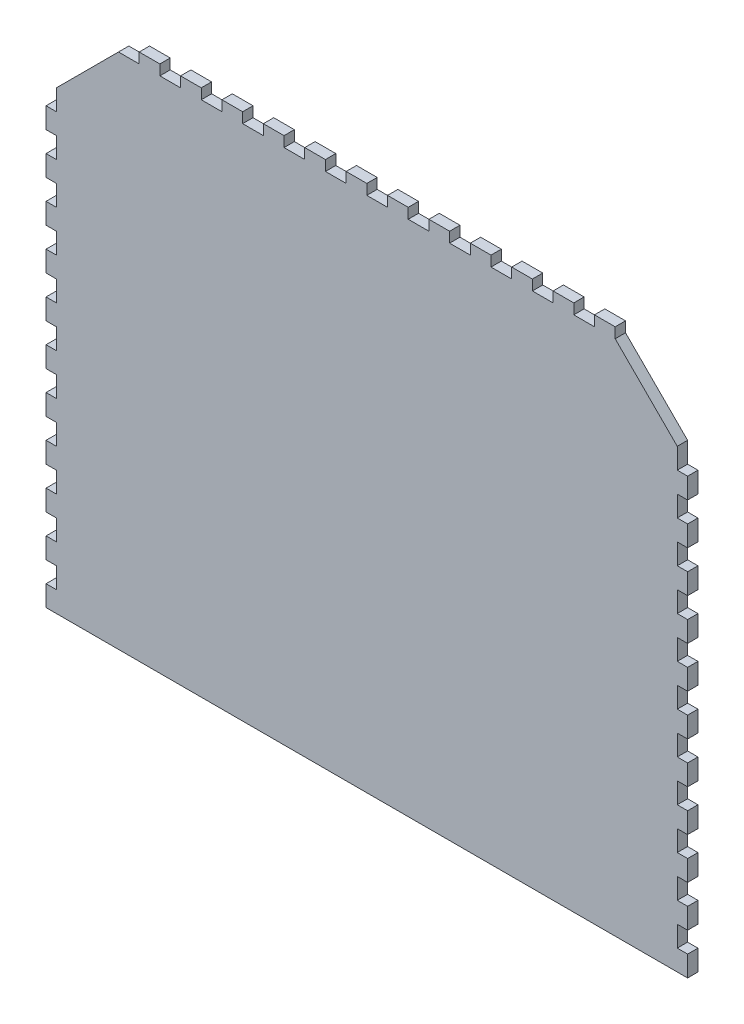
SolidWorks part; units mm, degrees
material "Buche"
ref_plane "Ebene vorne" through (0, 0, 0) normal (0, 0, 1) x (1, 0, 0)
ref_plane "Ebene oben" through (0, 0, 0) normal (0, 1, 0) x (1, 0, 0)
ref_plane "Ebene rechts" through (0, 0, 0) normal (1, 0, 0) x (0, 0, -1)
sketch "Skizze1" plane through (0, 0, 0) normal (0, 0, 1) x (1, 0, 0)
  line L0 (430.8962, 326.3402) -> (430.8962, 336.3402)
  line L1 (430.8962, 316.3402) -> (730.8962, 316.3402)
  line L2 (730.8962, 326.3402) -> (730.8962, 336.3402)
  line L3 (480.8962, 566.3402) -> (490.8962, 566.3402)
  line L4 (430.8962, 536.3402) -> (460.8962, 566.3402)
  line L5 (730.8962, 536.3402) -> (700.8962, 566.3402)
  line L6 (460.8962, 566.3402) -> (470.8962, 566.3402)
  line L7 (470.8962, 566.3402) -> (470.8962, 571.3402)
  line L8 (470.8962, 571.3402) -> (480.8962, 571.3402)
  line L9 (480.8962, 571.3402) -> (480.8962, 566.3402)
  line L10 (490.8962, 566.3402) -> (490.8962, 571.3402)
  line L11 (490.8962, 571.3402) -> (500.8962, 571.3402)
  line L12 (500.8962, 571.3402) -> (500.8962, 566.3402)
  line L13 (730.8962, 316.3402) -> (735.8962, 316.3402)
  line L14 (735.8962, 316.3402) -> (735.8962, 326.3402)
  line L15 (735.8962, 326.3402) -> (730.8962, 326.3402)
  line L16 (730.8962, 346.3402) -> (730.8962, 356.3402)
  line L17 (730.8962, 336.3402) -> (735.8962, 336.3402)
  line L18 (735.8962, 336.3402) -> (735.8962, 346.3402)
  line L19 (735.8962, 346.3402) -> (730.8962, 346.3402)
  line L20 (730.8962, 366.3402) -> (730.8962, 376.3402)
  line L21 (730.8962, 356.3402) -> (735.8962, 356.3402)
  line L22 (735.8962, 356.3402) -> (735.8962, 366.3402)
  line L23 (735.8962, 366.3402) -> (730.8962, 366.3402)
  line L24 (730.8962, 386.3402) -> (730.8962, 396.3402)
  line L25 (730.8962, 376.3402) -> (735.8962, 376.3402)
  line L26 (735.8962, 376.3402) -> (735.8962, 386.3402)
  line L27 (735.8962, 386.3402) -> (730.8962, 386.3402)
  line L28 (730.8962, 406.3402) -> (730.8962, 416.3402)
  line L29 (730.8962, 396.3402) -> (735.8962, 396.3402)
  line L30 (735.8962, 396.3402) -> (735.8962, 406.3402)
  line L31 (735.8962, 406.3402) -> (730.8962, 406.3402)
  line L32 (730.8962, 426.3402) -> (730.8962, 436.3402)
  line L33 (730.8962, 416.3402) -> (735.8962, 416.3402)
  line L34 (735.8962, 416.3402) -> (735.8962, 426.3402)
  line L35 (735.8962, 426.3402) -> (730.8962, 426.3402)
  line L36 (730.8962, 446.3402) -> (730.8962, 456.3402)
  line L37 (730.8962, 436.3402) -> (735.8962, 436.3402)
  line L38 (735.8962, 436.3402) -> (735.8962, 446.3402)
  line L39 (735.8962, 446.3402) -> (730.8962, 446.3402)
  line L40 (730.8962, 466.3402) -> (730.8962, 476.3402)
  line L41 (730.8962, 456.3402) -> (735.8962, 456.3402)
  line L42 (735.8962, 456.3402) -> (735.8962, 466.3402)
  line L43 (735.8962, 466.3402) -> (730.8962, 466.3402)
  line L44 (730.8962, 486.3402) -> (730.8962, 496.3402)
  line L45 (730.8962, 476.3402) -> (735.8962, 476.3402)
  line L46 (735.8962, 476.3402) -> (735.8962, 486.3402)
  line L47 (735.8962, 486.3402) -> (730.8962, 486.3402)
  line L48 (730.8962, 506.3402) -> (730.8962, 516.3402)
  line L49 (730.8962, 496.3402) -> (735.8962, 496.3402)
  line L50 (735.8962, 496.3402) -> (735.8962, 506.3402)
  line L51 (735.8962, 506.3402) -> (730.8962, 506.3402)
  line L52 (730.8962, 526.3402) -> (730.8962, 536.3402)
  line L53 (730.8962, 516.3402) -> (735.8962, 516.3402)
  line L54 (735.8962, 516.3402) -> (735.8962, 526.3402)
  line L55 (735.8962, 526.3402) -> (730.8962, 526.3402)
  line L56 (430.8962, 316.3402) -> (425.8962, 316.3402)
  line L57 (425.8962, 316.3402) -> (425.8962, 326.3402)
  line L58 (425.8962, 326.3402) -> (430.8962, 326.3402)
  line L59 (430.8962, 346.3402) -> (430.8962, 356.3402)
  line L60 (425.8962, 336.3402) -> (425.8962, 346.3402)
  line L61 (425.8962, 346.3402) -> (430.8962, 346.3402)
  line L62 (430.8962, 366.3402) -> (430.8962, 376.3402)
  line L63 (425.8962, 356.3402) -> (425.8962, 366.3402)
  line L64 (425.8962, 366.3402) -> (430.8962, 366.3402)
  line L65 (430.8962, 386.3402) -> (430.8962, 396.3402)
  line L66 (425.8962, 376.3402) -> (425.8962, 386.3402)
  line L67 (425.8962, 386.3402) -> (430.8962, 386.3402)
  line L68 (430.8962, 406.3402) -> (430.8962, 416.3402)
  line L69 (425.8962, 396.3402) -> (425.8962, 406.3402)
  line L70 (425.8962, 406.3402) -> (430.8962, 406.3402)
  line L71 (430.8962, 426.3402) -> (430.8962, 436.3402)
  line L72 (425.8962, 416.3402) -> (425.8962, 426.3402)
  line L73 (425.8962, 426.3402) -> (430.8962, 426.3402)
  line L74 (430.8962, 446.3402) -> (430.8962, 456.3402)
  line L75 (425.8962, 436.3402) -> (425.8962, 446.3402)
  line L76 (425.8962, 446.3402) -> (430.8962, 446.3402)
  line L77 (430.8962, 466.3402) -> (430.8962, 476.3402)
  line L78 (425.8962, 456.3402) -> (425.8962, 466.3402)
  line L79 (425.8962, 466.3402) -> (430.8962, 466.3402)
  line L80 (430.8962, 486.3402) -> (430.8962, 496.3402)
  line L81 (425.8962, 476.3402) -> (425.8962, 486.3402)
  line L82 (425.8962, 486.3402) -> (430.8962, 486.3402)
  line L83 (430.8962, 506.3402) -> (430.8962, 516.3402)
  line L84 (425.8962, 496.3402) -> (425.8962, 506.3402)
  line L85 (425.8962, 506.3402) -> (430.8962, 506.3402)
  line L86 (430.8962, 526.3402) -> (430.8962, 536.3402)
  line L87 (425.8962, 516.3402) -> (425.8962, 526.3402)
  line L88 (425.8962, 526.3402) -> (430.8962, 526.3402)
  line L89 (425.8962, 336.3402) -> (430.8962, 336.3402)
  line L90 (425.8962, 356.3402) -> (430.8962, 356.3402)
  line L91 (425.8962, 376.3402) -> (430.8962, 376.3402)
  line L92 (425.8962, 396.3402) -> (430.8962, 396.3402)
  line L93 (425.8962, 416.3402) -> (430.8962, 416.3402)
  line L94 (425.8962, 436.3402) -> (430.8962, 436.3402)
  line L95 (425.8962, 456.3402) -> (430.8962, 456.3402)
  line L96 (425.8962, 476.3402) -> (430.8962, 476.3402)
  line L97 (425.8962, 496.3402) -> (430.8962, 496.3402)
  line L98 (425.8962, 516.3402) -> (430.8962, 516.3402)
  line L99 (500.8962, 566.3402) -> (510.8962, 566.3402)
  line L100 (510.8962, 566.3402) -> (510.8962, 571.3402)
  line L101 (510.8962, 571.3402) -> (520.8962, 571.3402)
  line L102 (520.8962, 571.3402) -> (520.8962, 566.3402)
  line L103 (520.8962, 566.3402) -> (530.8962, 566.3402)
  line L104 (530.8962, 566.3402) -> (530.8962, 571.3402)
  line L105 (530.8962, 571.3402) -> (540.8962, 571.3402)
  line L106 (540.8962, 571.3402) -> (540.8962, 566.3402)
  line L107 (540.8962, 566.3402) -> (550.8962, 566.3402)
  line L108 (550.8962, 566.3402) -> (550.8962, 571.3402)
  line L109 (550.8962, 571.3402) -> (560.8962, 571.3402)
  line L110 (560.8962, 571.3402) -> (560.8962, 566.3402)
  line L111 (560.8962, 566.3402) -> (570.8962, 566.3402)
  line L112 (570.8962, 566.3402) -> (570.8962, 571.3402)
  line L113 (570.8962, 571.3402) -> (580.8962, 571.3402)
  line L114 (580.8962, 571.3402) -> (580.8962, 566.3402)
  line L115 (580.8962, 566.3402) -> (590.8962, 566.3402)
  line L116 (590.8962, 566.3402) -> (590.8962, 571.3402)
  line L117 (590.8962, 571.3402) -> (600.8962, 571.3402)
  line L118 (600.8962, 571.3402) -> (600.8962, 566.3402)
  line L119 (600.8962, 566.3402) -> (610.8962, 566.3402)
  line L120 (610.8962, 566.3402) -> (610.8962, 571.3402)
  line L121 (610.8962, 571.3402) -> (620.8962, 571.3402)
  line L122 (620.8962, 571.3402) -> (620.8962, 566.3402)
  line L123 (620.8962, 566.3402) -> (630.8962, 566.3402)
  line L124 (630.8962, 566.3402) -> (630.8962, 571.3402)
  line L125 (630.8962, 571.3402) -> (640.8962, 571.3402)
  line L126 (640.8962, 571.3402) -> (640.8962, 566.3402)
  line L127 (640.8962, 566.3402) -> (650.8962, 566.3402)
  line L128 (650.8962, 566.3402) -> (650.8962, 571.3402)
  line L129 (650.8962, 571.3402) -> (660.8962, 571.3402)
  line L130 (660.8962, 571.3402) -> (660.8962, 566.3402)
  line L131 (660.8962, 566.3402) -> (670.8962, 566.3402)
  line L132 (670.8962, 566.3402) -> (670.8962, 571.3402)
  line L133 (670.8962, 571.3402) -> (680.8962, 571.3402)
  line L134 (680.8962, 571.3402) -> (680.8962, 566.3402)
  line L135 (680.8962, 566.3402) -> (690.8962, 566.3402)
  line L136 (690.8962, 566.3402) -> (690.8962, 571.3402)
  line L137 (690.8962, 571.3402) -> (700.8962, 571.3402)
  line L138 (700.8962, 571.3402) -> (700.8962, 566.3402)
  dimension "D1" = 12
extrude "Aufsatz-Linear austragen1" add sketch "Skizze1" along normal blind 5
